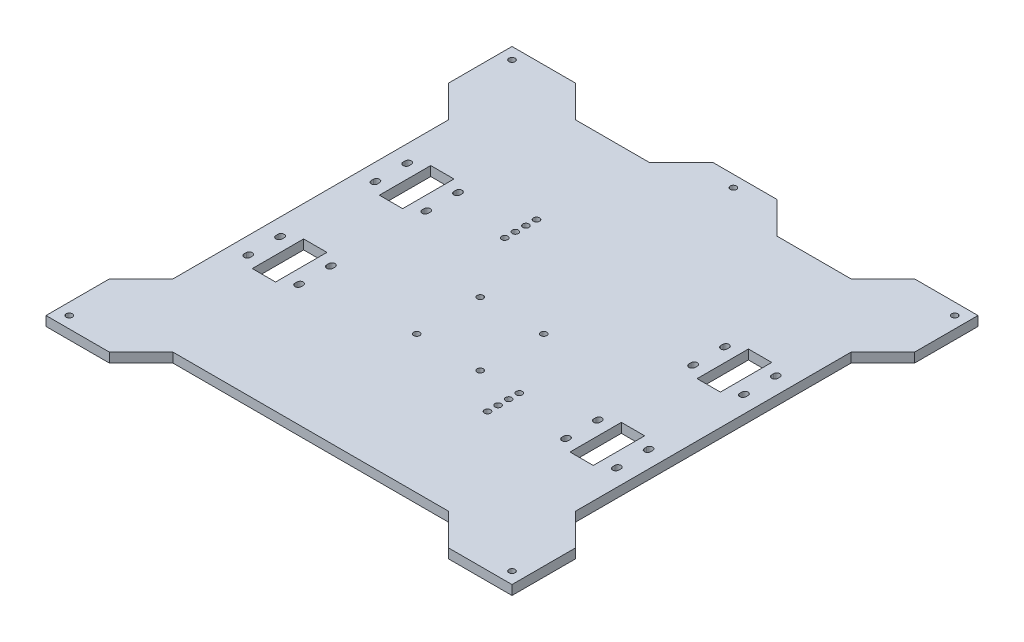
SolidWorks part; units mm, degrees
ref_plane "Front Plane" through (0, 0, 0) normal (0, 0, 1) x (1, 0, 0)
ref_plane "Top Plane" through (0, 0, 0) normal (0, 1, 0) x (1, 0, 0)
ref_plane "Right Plane" through (0, 0, 0) normal (1, 0, 0) x (0, 0, -1)
sketch "Sketch1" plane through (0, 0, 0) normal (0, 1, 0) x (1, 0, 0)
  line L1 (-110, 110) -> (110, 110)
  line L2 (-110, 110) -> (-110, -110)
  line L3 (-110, -110) -> (110, -110)
  line L4 (110, 110) -> (110, -110)
  line L5 (-110, 110) -> (110, -110) construction
  line L6 (-110, -110) -> (110, 110) construction
  point P0 (0, 0)
  dimension "D1" = 220
  dimension "D2" = 220
extrude "Square" add sketch "Sketch1" along normal blind 4.5
sketch "Sketch2" plane through (0, 4.5, 0) normal (0, 1, 0) x (1, 0, 0)
  line L0 (0, 110) -> (0, -110) construction
  line L1 (110, 110) -> (-110, 110) construction
  line L2 (-110, -110) -> (110, -110) construction
  line L3 (-110, 0) -> (110, 0) construction
  line L4 (-110, 110) -> (-110, -110) construction
  line L5 (110, -110) -> (110, 110) construction
  line L6 (75, 110) -> (75, -110) construction
  line L7 (75, 30) -> (0, 30) construction
  line L8 (75, -30) -> (0, -30) construction
  circle A0 centre (87, 38) radius 1.45
  circle A1 centre (87, 22) radius 1.45
  circle A2 centre (63, 22) radius 1.45
  circle A3 centre (63, 38) radius 1.45
  circle A4 centre (-63, 38) radius 1.45
  circle A5 centre (-63, 22) radius 1.45
  circle A6 centre (-87, 22) radius 1.45
  circle A7 centre (-87, 38) radius 1.45
  circle A8 centre (-87, 22) radius 1.45
  circle A9 centre (-87, 38) radius 1.45
  circle A10 centre (-63, 38) radius 1.45
  circle A11 centre (-63, 22) radius 1.45
  circle A12 centre (63, 22) radius 1.45
  circle A13 centre (63, 38) radius 1.45
  circle A14 centre (87, 38) radius 1.45
  circle A15 centre (87, 22) radius 1.45
  circle A16 centre (87, -22) radius 1.45
  circle A17 centre (87, -38) radius 1.45
  circle A18 centre (63, -38) radius 1.45
  circle A19 centre (63, -22) radius 1.45
  circle A20 centre (-63, -22) radius 1.45
  circle A21 centre (-63, -38) radius 1.45
  circle A22 centre (-87, -38) radius 1.45
  circle A23 centre (-87, -22) radius 1.45
  circle A24 centre (-87, -38) radius 1.45
  circle A25 centre (-87, -22) radius 1.45
  circle A26 centre (-63, -22) radius 1.45
  circle A27 centre (-63, -38) radius 1.45
  circle A28 centre (63, -38) radius 1.45
  circle A29 centre (63, -22) radius 1.45
  circle A30 centre (87, -22) radius 1.45
  circle A31 centre (87, -38) radius 1.45
  dimension "D6" = 2.9
  dimension "D7" = 2.9
  dimension "D1" = 75
  dimension "D2" = 30
  dimension "D3" = 16
  dimension "D5" = 12
extrude "LM8UU-Holders" cut sketch "Sketch2" against normal through all contours A7 | A6 | A5 | A4 | A20 | A21 | A22 | A23 | A19 | A18 | A17 | A16 | A1 | A0 | A3 | A2 region at (87, 4.5, -38) region at (87, 4.5, -22) region at (63, 4.5, -22) region at (63, 4.5, -38) region at (-63, 4.5, -38) region at (-63, 4.5, -22) region at (-87, 4.5, -22) region at (-87, 4.5, -38) region at (87, 4.5, 22) region at (87, 4.5, 38) region at (63, 4.5, 38) region at (63, 4.5, 22) region at (-63, 4.5, 22) region at (-63, 4.5, 38) region at (-87, 4.5, 38) region at (-87, 4.5, 22)
sketch "Sketch10" plane through (0, 4.5, 0) normal (0, 1, 0) x (1, 0, 0)
  line L0 (0, 110) -> (0, -79.9796) construction
  line L3 (-26.5242, 0) -> (110, 0) construction
  line L6 (75, 110) -> (75, -110) construction
  line L7 (75, 30) -> (-75, 30) construction
  line L8 (87, 22) -> (87, 23) construction
  line L9 (110, 110) -> (-110, 110) construction
  line L10 (110, -110) -> (110, 110) construction
  line L11 (85.55, 22) -> (85.55, 23)
  line L12 (88.45, 22) -> (88.45, 23)
  line L13 (87, 38) -> (87, 37) construction
  line L14 (88.45, 38) -> (88.45, 37)
  line L15 (85.55, 38) -> (85.55, 37)
  line L16 (63, 38) -> (63, 37) construction
  line L17 (61.55, 38) -> (61.55, 37)
  line L18 (64.45, 38) -> (64.45, 37)
  line L19 (63, 22) -> (63, 23) construction
  line L20 (64.45, 22) -> (64.45, 23)
  line L21 (61.55, 22) -> (61.55, 23)
  line L22 (75, -30) -> (-75, -30) construction
  line L23 (87, -22) -> (87, -23) construction
  line L24 (85.55, -22) -> (85.55, -23)
  line L25 (88.45, -22) -> (88.45, -23)
  line L26 (87, -38) -> (87, -37) construction
  line L27 (88.45, -38) -> (88.45, -37)
  line L28 (85.55, -38) -> (85.55, -37)
  line L29 (63, -38) -> (63, -37) construction
  line L30 (61.55, -38) -> (61.55, -37)
  line L31 (64.45, -38) -> (64.45, -37)
  line L32 (63, -22) -> (63, -23) construction
  line L33 (64.45, -22) -> (64.45, -23)
  line L34 (61.55, -22) -> (61.55, -23)
  line L35 (26.5242, 0) -> (-110, 0) construction
  line L36 (-87, 22) -> (-87, 23) construction
  line L37 (-85.55, 22) -> (-85.55, 23)
  line L38 (-88.45, 22) -> (-88.45, 23)
  line L39 (-87, 38) -> (-87, 37) construction
  line L40 (-88.45, 38) -> (-88.45, 37)
  line L41 (-85.55, 38) -> (-85.55, 37)
  line L42 (-63, 38) -> (-63, 37) construction
  line L43 (-61.55, 38) -> (-61.55, 37)
  line L44 (-64.45, 38) -> (-64.45, 37)
  line L45 (-63, 22) -> (-63, 23) construction
  line L46 (-64.45, 22) -> (-64.45, 23)
  line L47 (-61.55, 22) -> (-61.55, 23)
  line L48 (-87, -22) -> (-87, -23) construction
  line L49 (-85.55, -22) -> (-85.55, -23)
  line L50 (-88.45, -22) -> (-88.45, -23)
  line L51 (-87, -38) -> (-87, -37) construction
  line L52 (-88.45, -38) -> (-88.45, -37)
  line L53 (-85.55, -38) -> (-85.55, -37)
  line L54 (-63, -38) -> (-63, -37) construction
  line L55 (-61.55, -38) -> (-61.55, -37)
  line L56 (-64.45, -38) -> (-64.45, -37)
  line L57 (-63, -22) -> (-63, -23) construction
  line L58 (-64.45, -22) -> (-64.45, -23)
  line L59 (-61.55, -22) -> (-61.55, -23)
  arc A0 (61.55, 38) -> (64.45, 38) centre (63, 38) cw
  arc A1 (88.45, 38) -> (85.55, 38) centre (87, 38) ccw
  arc A2 (85.55, 22) -> (88.45, 22) centre (87, 22) ccw
  arc A3 (88.45, 23) -> (85.55, 23) centre (87, 23) ccw
  arc A4 (85.55, 37) -> (88.45, 37) centre (87, 37) ccw
  arc A5 (64.45, 37) -> (61.55, 37) centre (63, 37) cw
  arc A6 (64.45, 22) -> (61.55, 22) centre (63, 22) cw
  arc A7 (61.55, 23) -> (64.45, 23) centre (63, 23) cw
  arc A8 (85.55, -22) -> (88.45, -22) centre (87, -22) cw
  arc A9 (88.45, -23) -> (85.55, -23) centre (87, -23) cw
  arc A10 (88.45, -38) -> (85.55, -38) centre (87, -38) cw
  arc A11 (85.55, -37) -> (88.45, -37) centre (87, -37) cw
  arc A12 (61.55, -38) -> (64.45, -38) centre (63, -38) ccw
  arc A13 (64.45, -37) -> (61.55, -37) centre (63, -37) ccw
  arc A14 (64.45, -22) -> (61.55, -22) centre (63, -22) ccw
  arc A15 (61.55, -23) -> (64.45, -23) centre (63, -23) ccw
  arc A16 (-85.55, 22) -> (-88.45, 22) centre (-87, 22) cw
  arc A17 (-88.45, 23) -> (-85.55, 23) centre (-87, 23) cw
  arc A18 (-88.45, 38) -> (-85.55, 38) centre (-87, 38) cw
  arc A19 (-85.55, 37) -> (-88.45, 37) centre (-87, 37) cw
  arc A20 (-61.55, 38) -> (-64.45, 38) centre (-63, 38) ccw
  arc A21 (-64.45, 37) -> (-61.55, 37) centre (-63, 37) ccw
  arc A22 (-64.45, 22) -> (-61.55, 22) centre (-63, 22) ccw
  arc A23 (-61.55, 23) -> (-64.45, 23) centre (-63, 23) ccw
  arc A24 (-85.55, -22) -> (-88.45, -22) centre (-87, -22) ccw
  arc A25 (-88.45, -23) -> (-85.55, -23) centre (-87, -23) ccw
  arc A26 (-88.45, -38) -> (-85.55, -38) centre (-87, -38) ccw
  arc A27 (-85.55, -37) -> (-88.45, -37) centre (-87, -37) ccw
  arc A28 (-61.55, -38) -> (-64.45, -38) centre (-63, -38) cw
  arc A29 (-64.45, -37) -> (-61.55, -37) centre (-63, -37) cw
  arc A30 (-64.45, -22) -> (-61.55, -22) centre (-63, -22) cw
  arc A31 (-61.55, -23) -> (-64.45, -23) centre (-63, -23) cw
  point P8 (87, 22.5)
  point P19 (87, 37.5)
  point P28 (63, 37.5)
  point P35 (63, 22.5)
  point P44 (87, -22.5)
  point P51 (87, -37.5)
  point P58 (63, -37.5)
  point P65 (63, -22.5)
  point P73 (0, 30)
  point P74 (0, -30)
  point P76 (-87, 22.5)
  point P83 (-87, 37.5)
  point P90 (-63, 37.5)
  point P97 (-63, 22.5)
  point P104 (-87, -22.5)
  point P111 (-87, -37.5)
  point P118 (-63, -37.5)
  point P125 (-63, -22.5)
  dimension "D1" = 75
  dimension "D2" = 30
  dimension "D3" = 16
  dimension "D5" = 12
  dimension "D4" = 1.45
  dimension "D7" = 1.45
  dimension "D8" = 1
  dimension "D9" = 1
sketch "Sketch3" plane through (0, 4.5, 0) normal (0, 1, 0) x (1, 0, 0)
  line L0 (0, -110) -> (0, 110) construction
  line L1 (-110, -110) -> (110, -110) construction
  line L2 (110, 110) -> (-110, 110) construction
  line L3 (110, -15) -> (-110, -15) construction
  line L6 (15, -30) -> (-15, -30) construction
  line L7 (15, 0) -> (-15, 0) construction
  line L8 (110, -110) -> (110, 110) construction
  line L9 (-110, 110) -> (-110, -110) construction
  line L10 (110, 0) -> (-110, 0) construction
  circle A0 centre (-15, -30) radius 1.45
  circle A1 centre (15, -30) radius 1.45
  circle A2 centre (15, 0) radius 1.45
  circle A3 centre (-15, 0) radius 1.45
  point P16 (0, -30)
  dimension "D1" = 2.9
  dimension "D2" = 15
  dimension "D3" = 15
  dimension "D5" = 15
extrude "DefaultBelt" cut sketch "Sketch3" against normal through all
sketch "Sketch4" plane through (0, 4.5, 0) normal (0, 1, 0) x (1, 0, 0)
  line L0 (0, 110) -> (0, -110) construction
  line L1 (110, 110) -> (-110, 110) construction
  line L2 (-110, -110) -> (110, -110) construction
  line L3 (-15, -1.45) -> (-15, -28.55) construction
  line L4 (15, -28.55) -> (15, -1.45) construction
  line L5 (15, -15) -> (-15, -15) construction
  arc A0 (-0.7348, 6.25) -> (0.7348, 6.25) centre (0, 5) ccw
  arc A1 (0.7348, 6.25) -> (-0.7348, 6.25) centre (0, 7.5) ccw
  arc A2 (0.7348, -36.25) -> (-0.7348, -36.25) centre (0, -37.5) cw
  arc A3 (-0.7348, -36.25) -> (0.7348, -36.25) centre (0, -35) cw
  circle A4 centre (-15, 0) radius 1.45 construction
  circle A5 centre (-15, -30) radius 1.45 construction
  circle A6 centre (15, -30) radius 1.45 construction
  circle A7 centre (15, 0) radius 1.45 construction
  dimension "D1" = 2.9
  dimension "D2" = 2.9
  dimension "D3" = 20
  dimension "D4" = 22.5
extrude "BeltOptions" [suppressed] cut sketch "Sketch4" against normal through all
sketch "Sketch5" plane through (0, 4.5, 0) normal (0, 1, 0) x (1, 0, 0)
  line L0 (-110, 0) -> (110, 0) construction
  line L1 (-110, 110) -> (-110, -110) construction
  line L2 (110, -110) -> (110, 110) construction
  line L3 (0, 110) -> (0, -110) construction
  line L4 (110, 110) -> (-110, 110) construction
  line L5 (-110, 110) -> (-110, 80)
  line L6 (-110, 80) -> (-95, 65)
  line L7 (-95, 65) -> (-95, -65)
  line L8 (0, 0) -> (-110, 110) construction
  line L9 (-65, 95) -> (65, 95)
  line L10 (-80, 110) -> (-65, 95)
  line L11 (-110, 110) -> (-80, 110)
  line L12 (-95, 65) -> (-95, -65)
  line L13 (0, 0) -> (110, 110) construction
  line L14 (95, 65) -> (95, -65)
  line L15 (110, 110) -> (80, 110)
  line L16 (80, 110) -> (65, 95)
  line L17 (95, 65) -> (95, -65)
  line L18 (110, 80) -> (95, 65)
  line L19 (110, 110) -> (110, 80)
  line L20 (0, 0) -> (110, -110) construction
  line L21 (0, 0) -> (-110, -110) construction
  line L22 (110, -110) -> (110, -80)
  line L23 (110, -80) -> (95, -65)
  line L24 (80, -110) -> (65, -95)
  line L25 (110, -110) -> (80, -110)
  line L26 (-110, -110) -> (-80, -110)
  line L27 (-80, -110) -> (-65, -95)
  line L28 (-65, -95) -> (65, -95)
  line L29 (-110, -80) -> (-95, -65)
  line L30 (-110, -110) -> (-110, -80)
  point P24 (0, 95)
  point P32 (95, 0)
  point P35 (-95, 0)
  point P36 (0, -95)
  circle M16 centre (15, -30) radius 1.45
  circle M18 centre (63, 38) radius 1.45
  circle M20 centre (87, 22) radius 1.45
  circle M22 centre (87, -38) radius 1.45
  circle M23 centre (63, -38) radius 1.45
  circle M24 centre (63, -22) radius 1.45
  circle M25 centre (-87, -22) radius 1.45
  circle M26 centre (-87, -38) radius 1.45
  circle M27 centre (-63, -38) radius 1.45
  circle M28 centre (-63, -22) radius 1.45
  circle M29 centre (-63, 38) radius 1.45
  circle M30 centre (-63, 22) radius 1.45
  circle M31 centre (-87, 22) radius 1.45
  circle M32 centre (-87, 38) radius 1.45
  line M33 (110, -110) -> (110, 110)
  line M34 (110, 110) -> (-110, 110)
  line M35 (-110, 110) -> (-110, -110)
  line M36 (-110, -110) -> (110, -110)
  dimension "D1" = 15
  dimension "D2" = 30
  dimension "D3" = 45
  dimension "D4" = 45
extrude "Shaping" cut sketch "Sketch5" against normal blind 10 flip side to cut contours L29 L27 L28 L24 L23 L14 L18 L16 L9 L10 L6 L7 M35 M36 M33 M34 M16 M18 M20 M22 M24 M26 M28 M30 M32 M31 M29 M27 M25 M23 region at (0.037, 4.5, -0.0113)
sketch "Sketch6" plane through (0, 4.5, 0) normal (0, 1, 0) x (1, 0, 0)
  line L0 (-110, 110) -> (110, -110) construction
  line L1 (-110, -110) -> (110, 110) construction
  line L2 (110, 80) -> (110, 110) construction
  line L3 (0, 95) -> (0, -95) construction
  line L4 (-65, 95) -> (65, 95) construction
  line L5 (-65, -95) -> (65, -95) construction
  line L6 (-95, 0) -> (95, 0) construction
  line L7 (-95, 65) -> (-95, -65) construction
  line L8 (95, 65) -> (95, -65) construction
  circle A0 centre (-104.5, 104.5) radius 1.45
  circle A1 centre (104.5, 104.5) radius 1.45
  circle A2 centre (104.5, -104.5) radius 1.45
  circle A3 centre (-104.5, -104.5) radius 1.45
  dimension "D2" = 2.9
  dimension "D1" = 45
  dimension "D3" = 104.5
extrude "Cut-Extrude5" cut sketch "Sketch6" against normal through all
sketch "Sketch7" plane through (0, 4.5, 0) normal (0, 1, 0) x (1, 0, 0)
  line L0 (-87, 38) -> (-63, 22) construction
  line L1 (-63, 22) -> (-87, 22) construction
  line L2 (-87, 22) -> (-63, 38) construction
  line L3 (-63, 38) -> (-87, 38) construction
  line L4 (-95, 0) -> (95, 0) construction
  line L5 (-80.5, 42.125) -> (-69.5, 42.125)
  line L6 (-80.5, 42.125) -> (-80.5, 17.875)
  line L7 (-80.5, 17.875) -> (-69.5, 17.875)
  line L8 (-69.5, 42.125) -> (-69.5, 17.875)
  line L9 (-80.5, 42.125) -> (-69.5, 17.875) construction
  line L10 (-80.5, 17.875) -> (-69.5, 42.125) construction
  line L11 (-95, 65) -> (-95, -65) construction
  line L12 (95, 65) -> (95, -65) construction
  line L13 (0, -95) -> (0, 95) construction
  line L14 (-65, -95) -> (65, -95) construction
  line L15 (-65, 95) -> (65, 95) construction
  line L16 (-80.5, -17.875) -> (-69.5, -42.125) construction
  line L17 (-80.5, -42.125) -> (-69.5, -17.875) construction
  line L18 (-63, -38) -> (-87, -38) construction
  line L19 (-87, -22) -> (-63, -38) construction
  line L20 (-63, -22) -> (-87, -22) construction
  line L21 (-87, -38) -> (-63, -22) construction
  line L22 (-69.5, -42.125) -> (-69.5, -17.875)
  line L23 (-80.5, -17.875) -> (-69.5, -17.875)
  line L24 (-80.5, -42.125) -> (-80.5, -17.875)
  line L25 (-80.5, -42.125) -> (-69.5, -42.125)
  line L26 (-80.5, 17.875) -> (-69.5, 42.125) construction
  line L27 (80.5, 17.875) -> (69.5, 42.125) construction
  line L28 (87, -38) -> (63, -22) construction
  line L29 (63, -22) -> (87, -22) construction
  line L30 (87, -22) -> (63, -38) construction
  line L31 (63, -38) -> (87, -38) construction
  line L32 (80.5, -42.125) -> (69.5, -17.875) construction
  line L33 (80.5, -17.875) -> (69.5, -42.125) construction
  line L34 (80.5, 17.875) -> (69.5, 42.125) construction
  line L35 (80.5, 42.125) -> (69.5, 17.875) construction
  line L36 (63, 38) -> (87, 38) construction
  line L37 (87, 22) -> (63, 38) construction
  line L38 (63, 22) -> (87, 22) construction
  line L39 (87, 38) -> (63, 22) construction
  line L40 (80.5, -42.125) -> (69.5, -42.125)
  line L41 (80.5, -42.125) -> (80.5, -17.875)
  line L42 (80.5, -17.875) -> (69.5, -17.875)
  line L43 (69.5, -42.125) -> (69.5, -17.875)
  line L44 (69.5, 42.125) -> (69.5, 17.875)
  line L45 (80.5, 17.875) -> (69.5, 17.875)
  line L46 (80.5, 42.125) -> (80.5, 17.875)
  line L47 (80.5, 42.125) -> (69.5, 42.125)
  point P4 (-75, 30)
  point P33 (-75, -30)
  point P50 (75, -30)
  point P51 (75, 30)
  dimension "D1" = 11
  dimension "D2" = 24.25
extrude "Cut-Extrude6" cut sketch "Sketch7" against normal through all
sketch "Sketch8" plane through (0, 4.5, 0) normal (0, 1, 0) x (1, 0, 0)
  line L0 (0, 0) -> (0, 95) construction
  line L1 (0, 0) -> (-66.8115, 0) construction
  line L3 (-65, 95) -> (65, 95) construction
  line L4 (-33.45, 45) -> (-33.45, 30) construction
  line L5 (-33.45, 45) -> (-33.45, 30) construction
  line L6 (33.45, -45) -> (33.45, -30) construction
  circle A0 centre (-33.45, 45) radius 1.45
  circle A1 centre (-33.45, 40) radius 1.45
  circle A2 centre (-33.45, 35) radius 1.45
  circle A3 centre (-33.45, 30) radius 1.45
  circle A8 centre (33.45, -45) radius 1.45
  circle A9 centre (33.45, -40) radius 1.45
  circle A10 centre (33.45, -35) radius 1.45
  circle A11 centre (33.45, -30) radius 1.45
  dimension "D1" = 2.9
  dimension "D2" = 50
  dimension "D4" = 33.45
extrude "EndstopTrigger" cut sketch "Sketch8" against normal through all
pattern_linear "LPattern1" [suppressed] count 2 spacing 30 of bodies 108
sketch "Sketch9" plane through (0, 4.5, 0) normal (0, 1, 0) x (1, 0, 0)
  line L0 (-80, 110) -> (-110, 110) construction
  line L1 (-65, 95) -> (65, 95) construction
  line L7 (-95, 0) -> (95, 0) construction
  line L8 (-95, 65) -> (-95, -65) construction
  line L11 (95, 65) -> (95, -65) construction
  line L12 (-104.5, 104.5) -> (104.5, 104.5) construction
  line L13 (0, 110) -> (0, 95) construction
  line L14 (-80, 110) -> (80, 110) construction
  line L15 (15, 110) -> (30, 95)
  line L16 (-30, 95) -> (30, 95)
  line L17 (-15, 110) -> (-30, 95)
  line L18 (15, 110) -> (-15, 110)
  circle A1 centre (0, 104.5) radius 1.45
  dimension "D2" = 30
  dimension "D3" = 2.9
  dimension "D1" = 45
  dimension "D4" = 45
extrude "Boss-Extrude1" add sketch "Sketch9" against normal through all
extrude "HolesToSlots" cut sketch "Sketch10" against normal through all
sketch "Sketch11" plane through (0, 4.5, 0) normal (0, 1, 0) x (1, 0, 0)
  line L0 (0, -95) -> (0, 0) construction
  line L1 (-65, -95) -> (65, -95) construction
  line L2 (95, 0) -> (0, 0) construction
  line L3 (95, 65) -> (95, -65) construction
  line L4 (0, 0) -> (110, -110) construction
  line L5 (-69.1421, -85) -> (-5, -85)
  line L6 (-69.1421, -85) -> (-84.1421, -100)
  line L7 (-84.1421, -100) -> (-100, -100)
  line L8 (-100, -100) -> (-100, -84.1421)
  line L9 (-100, -84.1421) -> (-85, -69.1421)
  line L10 (-85, -69.1421) -> (-85, -52.125)
  line L11 (-85, -52.125) -> (-5, -52.125)
  line L12 (-80, -110) -> (-65, -95) construction
  line L13 (-110, -80) -> (-95, -65) construction
  line L14 (-110, -80) -> (-110, -110) construction
  line L15 (-110, -110) -> (-80, -110) construction
  line L16 (-80.5, -42.125) -> (-69.5, -42.125) construction
  line L17 (-95, 65) -> (-95, -65) construction
  line L18 (-5, -52.125) -> (-5, -85)
  line L19 (5, -52.125) -> (5, -85)
  line L20 (85, -52.125) -> (5, -52.125)
  line L21 (85, -69.1421) -> (85, -52.125)
  line L22 (100, -84.1421) -> (85, -69.1421)
  line L23 (100, -100) -> (100, -84.1421)
  line L24 (84.1421, -100) -> (100, -100)
  line L25 (69.1421, -85) -> (84.1421, -100)
  line L26 (69.1421, -85) -> (5, -85)
  line L27 (69.1421, 85) -> (5, 85)
  line L28 (69.1421, 85) -> (84.1421, 100)
  line L29 (84.1421, 100) -> (100, 100)
  line L30 (100, 100) -> (100, 84.1421)
  line L31 (100, 84.1421) -> (85, 69.1421)
  line L32 (85, 69.1421) -> (85, 52.125)
  line L33 (85, 52.125) -> (5, 52.125)
  line L34 (5, 52.125) -> (5, 85)
  line L35 (-5, 52.125) -> (-5, 85)
  line L36 (-85, 52.125) -> (-5, 52.125)
  line L37 (-85, 69.1421) -> (-85, 52.125)
  line L38 (-100, 84.1421) -> (-85, 69.1421)
  line L39 (-100, 100) -> (-100, 84.1421)
  line L40 (-84.1421, 100) -> (-100, 100)
  line L41 (-69.1421, 85) -> (-84.1421, 100)
  line L42 (-69.1421, 85) -> (-5, 85)
  dimension "D1" = 10
  dimension "D2" = 10
  dimension "D3" = 10
  dimension "D4" = 10
  dimension "D5" = 10
  dimension "D6" = 10
  dimension "D7" = 10
  dimension "D8" = 5
extrude "Cut-Extrude7" [suppressed] cut sketch "Sketch11" against normal through all
sketch "Sketch12" [suppressed] plane through (0, 4.5, 0) normal (0, 1, 0) x (1, 0, 0)
  line L0 (0, 0) -> (-110, -110) construction
  line L1 (-110, -110) -> (-80, -110) construction
  line L2 (-110, -80) -> (80, 110) construction
  line L3 (110, 80) -> (-80, -110) construction
  line L4 (-95, -65) -> (-65, -95) construction
  line L5 (0, 0) -> (0, -95) construction
  line L6 (-65, -95) -> (65, -95) construction
  line L7 (95, 0) -> (-95, 0) construction
  line L8 (-95, 65) -> (-95, -65) construction
  line L9 (-100, -100) -> (-100, -84.1421)
  line L10 (-100, -84.1421) -> (-59.2893, -43.4315)
  line L11 (-59.2893, -43.4315) -> (-43.4315, -43.4315)
  line L12 (-110, -80) -> (-110, -110) construction
  line L13 (-100, -100) -> (-84.1421, -100)
  line L14 (-84.1421, -100) -> (-43.4315, -59.2893)
  line L15 (-43.4315, -59.2893) -> (-43.4315, -43.4315)
  line L16 (55, -85) -> (-55, -85)
  line L17 (-55, -85) -> (-29.2893, -59.2893)
  line L18 (-29.2893, -59.2893) -> (29.2893, -59.2893)
  line L19 (95, -65) -> (65, -95) construction
  line L20 (0, 0) -> (110, -110) construction
  line L21 (55, -85) -> (29.2893, -59.2893)
  line L22 (43.4315, -59.2893) -> (43.4315, -43.4315)
  line L23 (84.1421, -100) -> (43.4315, -59.2893)
  line L24 (100, -100) -> (84.1421, -100)
  line L25 (59.2893, -43.4315) -> (43.4315, -43.4315)
  line L26 (100, -84.1421) -> (59.2893, -43.4315)
  line L27 (100, -100) -> (100, -84.1421)
  line L28 (95, 65) -> (65, 95) construction
  line L29 (-95, 65) -> (-65, 95) construction
  line L30 (100, 100) -> (100, 84.1421)
  line L31 (100, 84.1421) -> (59.2893, 43.4315)
  line L32 (59.2893, 43.4315) -> (43.4315, 43.4315)
  line L33 (100, 100) -> (84.1421, 100)
  line L34 (84.1421, 100) -> (43.4315, 59.2893)
  line L35 (43.4315, 59.2893) -> (43.4315, 43.4315)
  line L36 (55, 85) -> (29.2893, 59.2893)
  line L37 (-29.2893, 59.2893) -> (29.2893, 59.2893)
  line L38 (-55, 85) -> (-29.2893, 59.2893)
  line L39 (55, 85) -> (-55, 85)
  line L40 (-43.4315, 59.2893) -> (-43.4315, 43.4315)
  line L41 (-84.1421, 100) -> (-43.4315, 59.2893)
  line L42 (-100, 100) -> (-84.1421, 100)
  line L43 (-59.2893, 43.4315) -> (-43.4315, 43.4315)
  line L44 (-100, 84.1421) -> (-59.2893, 43.4315)
  line L45 (-100, 100) -> (-100, 84.1421)
  point P40 (0, -59.2893)
  point P41 (0, -85)
  point P67 (0, 85)
  point P68 (0, 59.2893)
  dimension "D1" = 10
  dimension "D2" = 10
  dimension "D3" = 80
  dimension "D4" = 10
  dimension "D5" = 10
  dimension "D6" = 0
extrude "Cut-Extrude8" [suppressed] cut sketch "Sketch12" against normal through all
sketch "Sketch14" [suppressed] plane through (0, 4.5, 0) normal (0, 1, 0) x (1, 0, 0)
  line L0 (0, 85) -> (0, 110) construction
  line L1 (55, 85) -> (-55, 85) construction
  line L2 (15, 110) -> (-15, 110) construction
  line L3 (10.8579, 100) -> (-10.8579, 100)
  line L4 (-10.8579, 100) -> (-25.8579, 85)
  line L5 (-25.8579, 85) -> (25.8579, 85)
  line L6 (-15, 110) -> (-30, 95) construction
  line L7 (10.8579, 100) -> (25.8579, 85)
  point P13 (0, 100)
  dimension "D1" = 10
  dimension "D2" = 10
extrude "Cut-Extrude10" [suppressed] cut sketch "Sketch14" against normal through all
sketch "Sketch13" [suppressed] plane through (0, 4.5, 0) normal (0, 1, 0) x (1, 0, 0)
  line L0 (-59.2893, 43.4315) -> (-59.2893, -43.4315) construction
  line L1 (-100, 84.1421) -> (-59.2893, 43.4315) construction
  line L2 (-59.2893, 0) -> (0, 0) construction
  line L3 (-59.2893, 33.4315) -> (-59.2893, -33.4315)
  line L4 (-59.2893, -33.4315) -> (-43.4315, -33.4315)
  line L5 (-43.4315, -33.4315) -> (-43.4315, 33.4315)
  line L6 (-43.4315, 33.4315) -> (-59.2893, 33.4315)
  line L7 (-59.2893, 43.4315) -> (-43.4315, 43.4315) construction
  line L8 (-43.4315, -43.4315) -> (-59.2893, -43.4315) construction
  line L9 (-43.4315, 43.4315) -> (-43.4315, 59.2893) construction
  line L10 (0, 0) -> (0, 43.4315) construction
  line L11 (59.2893, 43.4315) -> (59.2893, -43.4315) construction
  line L12 (43.4315, 33.4315) -> (59.2893, 33.4315)
  line L13 (43.4315, -33.4315) -> (43.4315, 33.4315)
  line L14 (59.2893, -33.4315) -> (43.4315, -33.4315)
  line L15 (59.2893, 33.4315) -> (59.2893, -33.4315)
  line L16 (110, -110) -> (0, 0) construction
  line L17 (55, -85) -> (29.2893, -59.2893) construction
  line L18 (-33.4315, -43.2893) -> (33.4315, -43.2893)
  line L19 (-33.4315, -43.2893) -> (-33.4315, -63.4315)
  line L20 (-33.4315, -63.4315) -> (33.4315, -63.4315)
  line L21 (33.4315, -43.2893) -> (33.4315, -63.4315)
  line L22 (-33.4315, -43.2893) -> (33.4315, -63.4315) construction
  line L23 (-33.4315, -63.4315) -> (33.4315, -43.2893) construction
  line L24 (-43.4315, -59.2893) -> (-43.4315, -43.4315) construction
  line L25 (0, -53.3604) -> (0, -63.4315) construction
  line L26 (55, 85) -> (25.8579, 85) construction
  line L28 (43.4315, -43.4315) -> (43.4315, -59.2893) construction
  line L29 (29.2893, -59.2893) -> (-29.2893, -59.2893) construction
  line L30 (43.4315, 59.2893) -> (43.4315, 43.4315) construction
  line L31 (-33.4315, 83) -> (33.4315, 83)
  line L32 (-33.4315, 83) -> (-33.4315, 15)
  line L33 (-33.4315, 15) -> (33.4315, 15)
  line L34 (33.4315, 83) -> (33.4315, 15)
  line L35 (-33.4315, 83) -> (33.4315, 15) construction
  line L36 (-33.4315, 15) -> (33.4315, 83) construction
  point P27 (0, -53.3604)
  point P43 (0, 49)
  dimension "D1" = 10
  dimension "D2" = 10
  dimension "D3" = 10
  dimension "D4" = 10
  dimension "D5" = 16
  dimension "D6" = 10
  dimension "D7" = 10
  dimension "D8" = 15
  dimension "D9" = 2
extrude "Cut-Extrude9" [suppressed] cut sketch "Sketch13" against normal through all
sketch "Sketch15" [suppressed] plane through (0, 4.5, 0) normal (0, 1, 0) x (1, 0, 0)
  line L0 (-59.2893, 0) -> (-95, 0) construction
  line L1 (-59.2893, 33.4315) -> (-59.2893, -33.4315) construction
  line L2 (-95, 65) -> (-95, -65) construction
  line L3 (-80.5, 17.875) -> (-69.5, 17.875) construction
  line L4 (-59.2893, -15) -> (-59.2893, -7.875)
  line L5 (-85, -7.875) -> (-85, 7.875)
  line L6 (-85, 7.875) -> (-66.4143, 7.875)
  line L7 (-59.2893, -7.875) -> (-59.2893, 7.875)
  line L8 (-66.4143, -7.875) -> (-59.2893, -15)
  line L9 (-85, -7.875) -> (-66.4143, -7.875)
  line L11 (-66.4143, 7.875) -> (-59.2893, 15)
  line L12 (-59.2893, 15) -> (-59.2893, 7.875)
  line L13 (0, 0) -> (0, -21.7485) construction
  line L14 (59.2893, 0) -> (95, 0) construction
  line L15 (59.2893, 15) -> (59.2893, 7.875)
  line L16 (66.4143, 7.875) -> (59.2893, 15)
  line L17 (85, -7.875) -> (66.4143, -7.875)
  line L18 (66.4143, -7.875) -> (59.2893, -15)
  line L19 (59.2893, -7.875) -> (59.2893, 7.875)
  line L20 (85, 7.875) -> (66.4143, 7.875)
  line L21 (85, -7.875) -> (85, 7.875)
  line L22 (59.2893, -15) -> (59.2893, -7.875)
  line L23 (-59.2893, 0) -> (-95, 0) construction
  point P17 (-85, 0)
  point P30 (85, 0)
  dimension "D1" = 10
  dimension "D2" = 10
  dimension "D4" = 45
  dimension "D5" = 15
extrude "Cut-Extrude11" [suppressed] cut sketch "Sketch15" against normal through all
sketch "Sketch16" [suppressed] plane through (0, 4.5, 0) normal (0, 1, 0) x (1, 0, 0)
  line L0 (-85, -69.1421) -> (-85, -52.125)
  line L1 (-59.2893, -43.4315) -> (-100, -84.1421) construction
  line L2 (-85, -52.125) -> (-67.9829, -52.125)
  line L3 (-67.9829, -52.125) -> (-85, -69.1421)
  line L4 (-95, 65) -> (-95, -65) construction
  line L5 (-80.5, -42.125) -> (-69.5, -42.125) construction
  line L6 (-95, 0) -> (95, 0) construction
  line L7 (95, 65) -> (95, -65) construction
  line L8 (0, 0) -> (0, -95) construction
  line L9 (-65, -95) -> (65, -95) construction
  line L10 (-67.9829, 52.125) -> (-85, 69.1421)
  line L11 (-85, 52.125) -> (-67.9829, 52.125)
  line L12 (-85, 69.1421) -> (-85, 52.125)
  line L13 (-67.9829, -52.125) -> (-85, -69.1421)
  line L14 (67.9829, -52.125) -> (85, -69.1421)
  line L15 (85, 69.1421) -> (85, 52.125)
  line L16 (85, 52.125) -> (67.9829, 52.125)
  line L17 (67.9829, 52.125) -> (85, 69.1421)
  line L18 (67.9829, -52.125) -> (85, -69.1421)
  line L19 (85, -52.125) -> (67.9829, -52.125)
  line L20 (85, -69.1421) -> (85, -52.125)
  line L21 (100, -84.1421) -> (59.2893, -43.4315) construction
  line L23 (69.5, -42.125) -> (80.5, -42.125) construction
  line L24 (80.5, 42.125) -> (69.5, 42.125) construction
  line L25 (59.2893, 43.4315) -> (100, 84.1421) construction
  line L26 (-100, 84.1421) -> (-59.2893, 43.4315) construction
  line L27 (-69.5, 42.125) -> (-80.5, 42.125) construction
  dimension "D1" = 10
  dimension "D2" = 10
  dimension "D3" = 10
  dimension "D4" = 10
  dimension "D5" = 10
  dimension "D6" = 10
  dimension "D7" = 10
  dimension "D8" = 10
extrude "Cut-Extrude12" [suppressed] cut sketch "Sketch16" against normal through all contours L3 L2 L0 | L10 L12 L11 | L17 L16 L15 | L14 L20 L19
equation "\"X-ROD-SPACING\"=45"
equation "\"Y-ROD-SPACING\"=75"
equation "\"Z-ROD-SPACING\"=17.5"
equation "\"Y-BED-OFFSET\"=2"
equation "\"Y-BED-ROD-INSET\"=3.5"
equation "\"T-SLOT-NUT-FILLET-RADIUS\"=0.5"
equation "\"T-SLOT-SCREW-SHAFT-RADIUS\"=1.55"
equation "\"T-SLOT-SCREW-SHAFT-CUTOUT-LENGTH\"=11.0"
equation "\"T-SLOT-NUT-DEPTH\"=3.5"
equation "\"T-SLOT-NUT-WIDTH\"=2.85"
equation "\"T-SLOT-NUT-END-DISTANCE\"=8"
equation "\"ACRYLIC-THICKNESS\"=10"
equation "\"ACRYLIC-THICKNESS2\"=4.5"
equation "\"ACRYLIC-TAB-CUTOUT-SIZE\"=\"ACRYLIC-THICKNESS\"+\"ACRYLIC-TAB-TOLERANCE\"*2"
equation "\"ACRYLIC-TAB-WIDTH\"=\"ACRYLIC-THICKNESS\""
equation "\"ACRYLIC-M3-HOLE\"=2.9"
equation "\"SMOOTHROD-CAP-SCREW-DISTANCE\"=20"
equation "\"FRAME-WIDTH-INNER\"=370"
equation "\"NEMA17-HOLE-SPACING\"=31"
equation "\"NEMA17-CENTRAL-CUTOUT\"=22.5"
equation "\"Z-BRACKET-REACH\"=55"
equation "\"TOP-BRACKET-SPACING\"=40"
equation "\"SMOOTHROD-X-LENGTH\"=350"
equation "\"SMOOTHROD-Y-LENGTH\"=350"
equation "\"SMOOTHROD-Z-LENGTH\"=350"
equation "\"SMOOTHROD-TIGHTENING-HEADROOM\"=.25"
equation "\"LEADSCREW-Z-LENGTH\"=300"
equation "\"SCREW-LENGTH-FRAME\"=\"ACRYLIC-THICKNESS\" + 10"
equation "\"SCREW-HEAD-RADIUS\"=6"
equation "\"PRINTED-X-SMOOTHROD-DIAMETER\"=9.0"
equation "\"PRINTED-X-SMOOTHROD-CUTOUT\"=10"
equation "\"PRINTED-X-BASE-HEIGHT\"=10"
equation "\"PRINTED-LM8UU-CUTOUT-SIZE\"=15.5"
equation "\"PRINTED-LM8UU-CUTOUT-LENGTH\"=24.5"
equation "\"PRINTED-X-IDLER-HEIGHT\"=16"
equation "\"PSU-MOUNTING-WIDTH\"=95"
equation "\"PSU-MOUNTING-HEIGHT\"=177"
equation "\"Y-BELT-TO-ROD-DISTANCE\"=20"
equation "\"D6@Sketch2\"=\"ACRYLIC-M3-HOLE\""
equation "\"D7@Sketch2\"=\"ACRYLIC-M3-HOLE\""
equation "\"D1@Sketch2\"=\"Y-ROD-SPACING\""
equation "\"D1@Sketch3\"=\"ACRYLIC-M3-HOLE\""
equation "\"D2@Sketch6\"=\"ACRYLIC-M3-HOLE\""
equation "\"Y-BED-SCREW-SPACING\"=209"
equation "\"Y-BED-SCREW-CUTOUT-SLOT-HEIGHT\"=2"
equation "\"ACRYLIC-TAB-TOLERANCE\"=-.05"
equation "\"Z-ROD-INSET\"=16"
equation "\"SCREW-LENGTH-MOTOR\"=\"ACRYLIC-THICKNESS\" + 5"
equation "\"SCREW-LENGTH-EXTRUDER\"=28"
equation "\"PRINTED-M3-HOLE\"=3.5"
equation "\"SPOOL-HOLDER-ROD-SPACING\"=150"
equation "\"ACRYLIC-X-CARRIAGE-WIDTH\"=55"
equation "\"ACRYLIC-X-CARRIAGE-HEIGHT\"=75"
equation "\"ACRYLIC-X-CARRIAGE-LM8UU-CUTOUT-WIDTH\"=24.25"
equation "\"ACRYLIC-X-CARRIAGE-LM8UU-CUTOUT-HEIGHT\"=11.0"
equation "\"ACRYLIC-X-CARRIAGE-SCREW-SPACING-X\"=15"
equation "\"ACRYLIC-X-CARRIAGE-SCREW-SPACING-Y\"=33"
equation "\"ACRYLIC-X-CARRIAGE-CENTER-TAB-SPACING\"=14"
equation "\"ACRYLIC-X-CARRIAGE-EXTRUDER-OFFSET\"=26"
equation "\"ACRYLIC-X-CARRIAGE-EXTRUDER-ANGLE\"=90"
equation "\"ACRYLIC-X-CARRIAGE-EXTRUDER-SHELF-DEPTH\"=\"ACRYLIC-X-CARRIAGE-EXTRUDER-OFFSET\" + 28"
equation "\"ACRYLIC-X-CARRIAGE-EXTRUDER-BRACE-SPACING\"=23"
equation "\"ACRYLIC-X-CARRIAGE-EXTRUDER-BRACE-TAB-OFFSET\"=20"
equation "\"ACRYLIC-X-CARRIAGE-EXTRUDER-BRACE-HEIGHT\"=35"
equation "\"ACRYLIC-X-CARRIAGE-EXTRUDER-BRACE-SCREW-SPACING\"=22"
equation "\"ACRYLIC-X-CARRIAGE-DUAL-WIDTH-MULTIPLIER\"=1.65"
equation "\"ACRYLIC-X-CARRIAGE-DUAL-HOTEND-SPACING\"=42"
equation "\"ACRYLIC-X-CARRIAGE-DUAL-WIDTH\"=75"
equation "\"ACRYLIC-X-CARRIAGE-DUAL-HOTEND-SEPARATION\"=36"
equation "\"ACRYLIC-X-CARRIAGE-DUAL-MOUNT-PLATE-DEPTH\"=75"
equation "\"ACRYLIC-X-CARRIAGE-DUAL-MOUNT-BRACE-WIDTH\"=33"
equation "\"ACRYLIC-X-CARRIAGE-DUAL-MOUNT-SCREW-WIDTH\"=40"
equation "\"BLOWER-FAN-WIDTH\"=15"
equation "\"D1@Sketch7\"=\"ACRYLIC-X-CARRIAGE-LM8UU-CUTOUT-HEIGHT\""
equation "\"D2@Sketch7\"=\"ACRYLIC-X-CARRIAGE-LM8UU-CUTOUT-WIDTH\""
equation "\"D1@Sketch8\"=\"ACRYLIC-M3-HOLE\""
equation "\"D2@Sketch4\"=\"ACRYLIC-M3-HOLE\""
equation "\"D1@Sketch4\"=\"ACRYLIC-M3-HOLE\""
equation "\"D3@Sketch4\"=20"
equation "\"D3@Sketch9\"=\"ACRYLIC-M3-HOLE\""
equation "\"D4@Sketch10\"=\"ACRYLIC-M3-HOLE\"/2"
equation "\"D7@Sketch10\"=\"ACRYLIC-M3-HOLE\" / 2"
